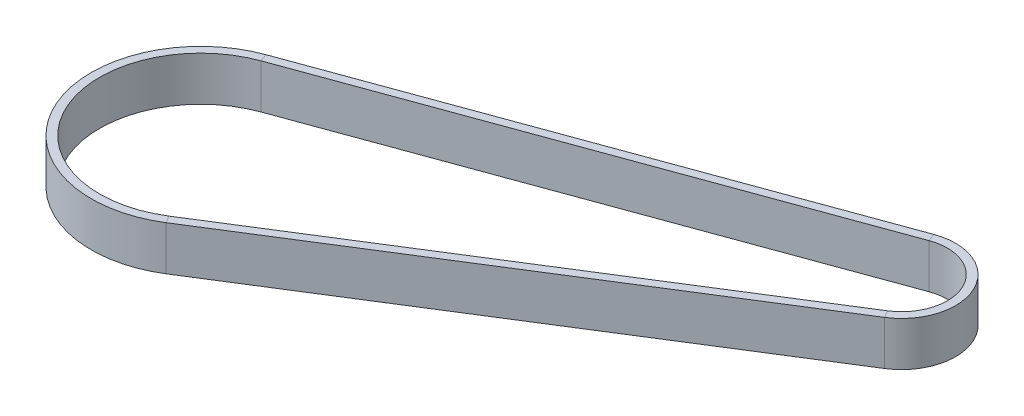
SolidWorks part; units mm, degrees
ref_plane "Front Plane" through (0, 0, 0) normal (0, 0, 1) x (1, 0, 0)
ref_plane "Top Plane" through (0, 0, 0) normal (0, 1, 0) x (1, 0, 0)
ref_plane "Right Plane" through (0, 0, 0) normal (1, 0, 0) x (0, 0, -1)
ref_axis "X" through (-88.99, 0, 0) along (1, 0, 0)
ref_axis "Y" through (0, 0, -88.99) along (0, 0, 1)
ref_axis "Z" through (0, 55, 0) along (0, -1, 0)
sketch "Sketch1" plane through (0, 0, 0) normal (0, 1, 0) x (1, 0, 0)
  line L0 (-21.9078, 552.7145) -> (154.9327, 617.1069)
  line L1 (170.6673, 584.9518) -> (11.3096, 484.8315)
  arc A0 (-21.9078, 552.7145) -> (11.3096, 484.8315) centre (-8.9061, 517.008) ccw
  arc A1 (170.6673, 584.9518) -> (154.9327, 617.1069) centre (161.0914, 600.1933) ccw
  point P2 (-8.9061, 517.008)
  dimension "D1" = 38
  dimension "D2" = 18
ref_plane "Plane1" through (11.3096, 0, -484.8315) normal (-0.8468, 0, 0.532) x (0.532, 0, 0.8468)
sketch "Sketch2" plane through (11.3096, 0, -484.8315) normal (-0.8468, 0, 0.532) x (0.532, 0, 0.8468)
  line L0 (0, 0) -> (-35.598, 0) construction
  line L1 (-1.5, 8) -> (1.5, 8)
  line L2 (-1.5, 8) -> (-1.5, -8)
  line L3 (-1.5, -8) -> (1.5, -8)
  line L4 (1.5, 8) -> (1.5, -8)
  line L5 (-1.5, 8) -> (1.5, -8) construction
  line L6 (-1.5, -8) -> (1.5, 8) construction
  point P0 (0, 0)
  dimension "D1" = 3
  dimension "D2" = 16
sweep "Sweep1" add profiles "Sketch2" path "Sketch1"
